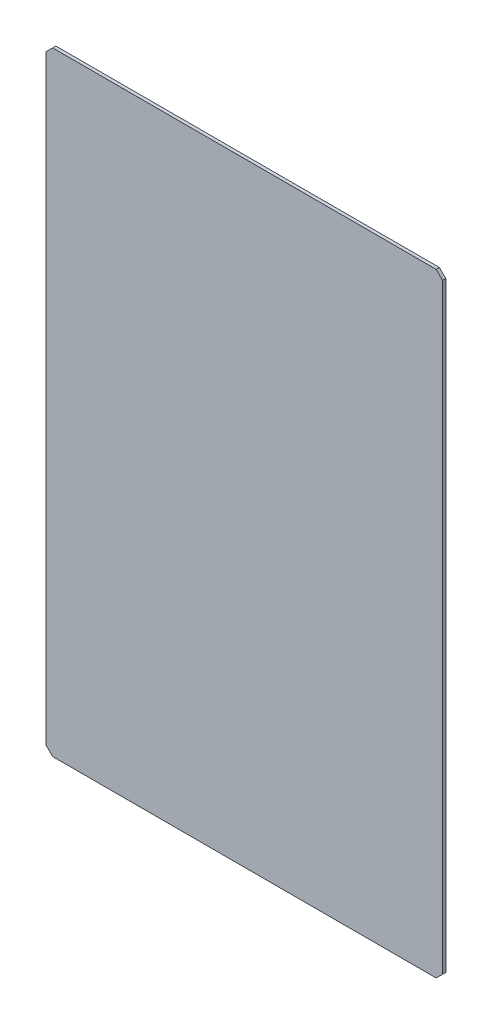
SolidWorks part; units mm, degrees
material "PET"
ref_plane "Front" through (0, 0, 0) normal (0, 0, 1) x (1, 0, 0)
ref_plane "Top" through (0, 0, 0) normal (0, 1, 0) x (1, 0, 0)
ref_plane "Right" through (0, 0, 0) normal (1, 0, 0) x (0, 0, -1)
ref_axis "Axis1" through (0, 0, 55) along (0, 0, -1)
sketch "Sketch1" plane through (0, 0, 0) normal (0, 0, 1) x (1, 0, 0)
  line L1 (-98.425, 152.4) -> (98.425, 152.4)
  line L2 (-98.425, 152.4) -> (-98.425, -152.4)
  line L3 (-98.425, -152.4) -> (98.425, -152.4)
  line L4 (98.425, 152.4) -> (98.425, -152.4)
  line L5 (-98.425, 152.4) -> (98.425, -152.4) construction
  line L6 (-98.425, -152.4) -> (98.425, 152.4) construction
  point P0 (0, 0)
  dimension "D1" = 304.8
  dimension "D2" = 196.85
extrude "Boss-Extrude1" add sketch "Sketch1" along normal blind 1.5875
chamfer "Chamfer1" distance 3.175 angle 45 4 edges at (-98.425, -152.4, 0.7937) (98.425, -152.4, 0.7937) (-98.425, 152.4, 0.7937) (98.425, 152.4, 0.7937)
